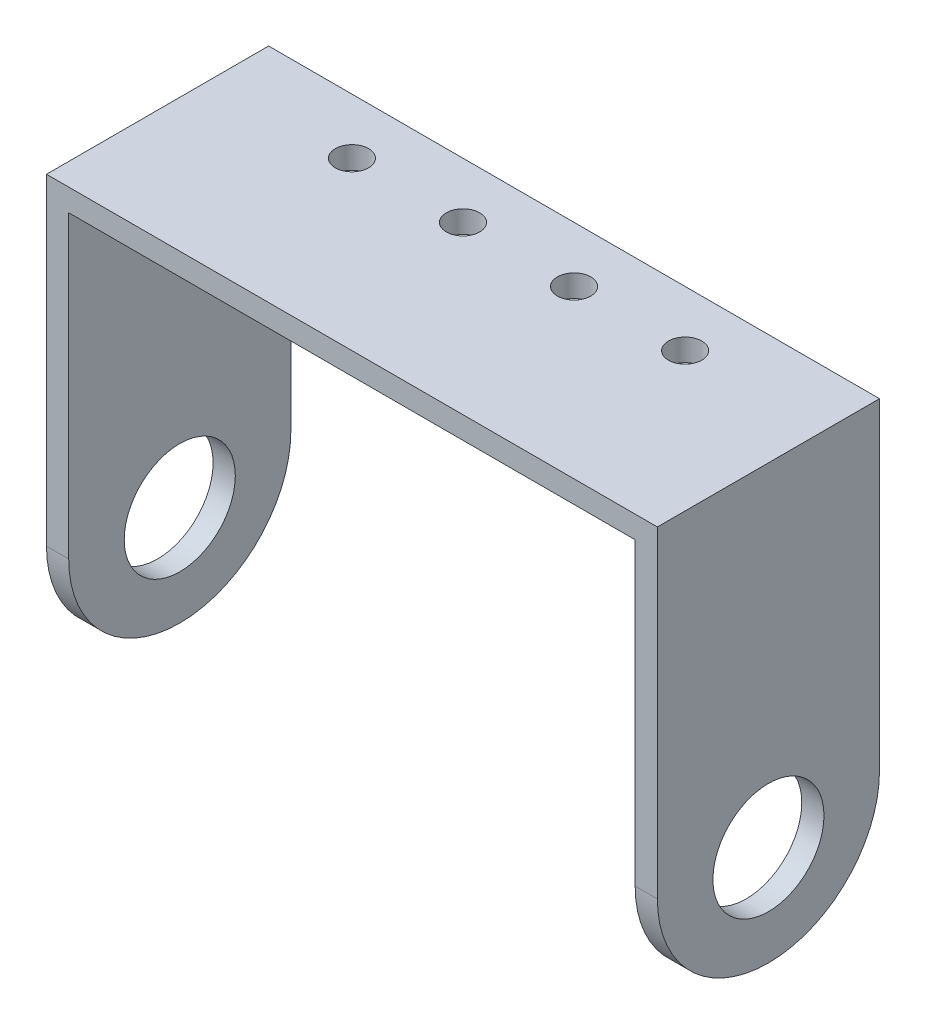
SolidWorks part; units mm, degrees
ref_plane "Front Plane" through (0, 0, 0) normal (0, 0, 1) x (1, 0, 0)
ref_plane "Top Plane" through (0, 0, 0) normal (0, 1, 0) x (1, 0, 0)
ref_plane "Right Plane" through (0, 0, 0) normal (1, 0, 0) x (0, 0, -1)
sketch "Sketch1" plane through (0, 0, 0) normal (0, 1, 0) x (1, 0, 0)
  line L1 (-27.5, 10) -> (27.5, 10)
  line L2 (-27.5, 10) -> (-27.5, -10)
  line L3 (-27.5, -10) -> (27.5, -10)
  line L4 (27.5, 10) -> (27.5, -10)
  line L5 (-27.5, 10) -> (27.5, -10) construction
  line L6 (-27.5, -10) -> (27.5, 10) construction
  point P0 (0, 0)
  dimension "D1" = 20
  dimension "D2" = 55
extrude "Boss-Extrude1" add sketch "Sketch1" against normal blind 2
sketch "Sketch2" plane through (0, -2, 0) normal (0, -1, 0) x (1, 0, 0)
  line L0 (27.5, -10) -> (-27.5, -10) construction
  line L1 (-27.5, 10) -> (-25.5, 10)
  line L2 (-27.5, 10) -> (-27.5, -10)
  line L3 (-27.5, -10) -> (-25.5, -10)
  line L4 (-25.5, 10) -> (-25.5, -10)
  line L6 (27.5, 10) -> (25.5, 10)
  line L7 (27.5, 10) -> (27.5, -10)
  line L8 (27.5, -10) -> (25.5, -10)
  line L9 (25.5, 10) -> (25.5, -10)
  dimension "D1" = 2
  dimension "D2" = 2
extrude "Boss-Extrude2" add sketch "Sketch2" along normal blind 37
sketch "Sketch3" plane through (27.5, 0, 0) normal (1, 0, 0) x (0, 0, -1)
  line L0 (10, -39) -> (-10, -39) construction
  line L1 (10, -39) -> (10, 0) construction
  circle A0 centre (0, -30) radius 5
  dimension "D1" = 10
  dimension "D3" = 10
  dimension "D2" = 9
extrude "Cut-Extrude1" cut sketch "Sketch3" against normal through all
sketch "Sketch4" plane through (-27.5, 0, 0) normal (-1, 0, 0) x (0, 0, 1)
  line L4 (10, 0) -> (-10, 0)
  line L5 (-10, 0) -> (-10, -39)
  line L6 (-10, -39) -> (10, -39)
  line L7 (10, -39) -> (10, 0)
  line L8 (10, 0) -> (-10, 0)
  line L9 (-10, 0) -> (-10, -39)
  line L10 (-10, -39) -> (10, -39)
  line L11 (10, -39) -> (10, 0)
  circle A0 centre (0, -29) radius 10
  line M7 (-10, 0) -> (-10, -39)
  line M8 (-10, -39) -> (10, -39)
  line M9 (10, -39) -> (10, 0)
  dimension "D2" = 20
  dimension "D1" = 0
extrude "Cut-Extrude2" cut sketch "Sketch4" against normal through all contours A0 M7 M8 | A0 L10 M9 region at (-27.5, -36.7663, 7.7663) region at (-27.5, -36.7663, -7.7663)
sketch "Sketch5" plane through (0, 0, 0) normal (0, 1, 0) x (1, 0, 0)
  line L0 (0, 0) -> (0, 13.488) construction
  circle A0 centre (5, 5) radius 1.5
  circle A1 centre (15, 5) radius 1.5
  circle A2 centre (-15, 5) radius 1.5
  circle A3 centre (-5, 5) radius 1.5
  dimension "D1" = 5
  dimension "D2" = 15
  dimension "D3" = 3
  dimension "D4" = 5
extrude "Cut-Extrude3" cut sketch "Sketch5" against normal through all
